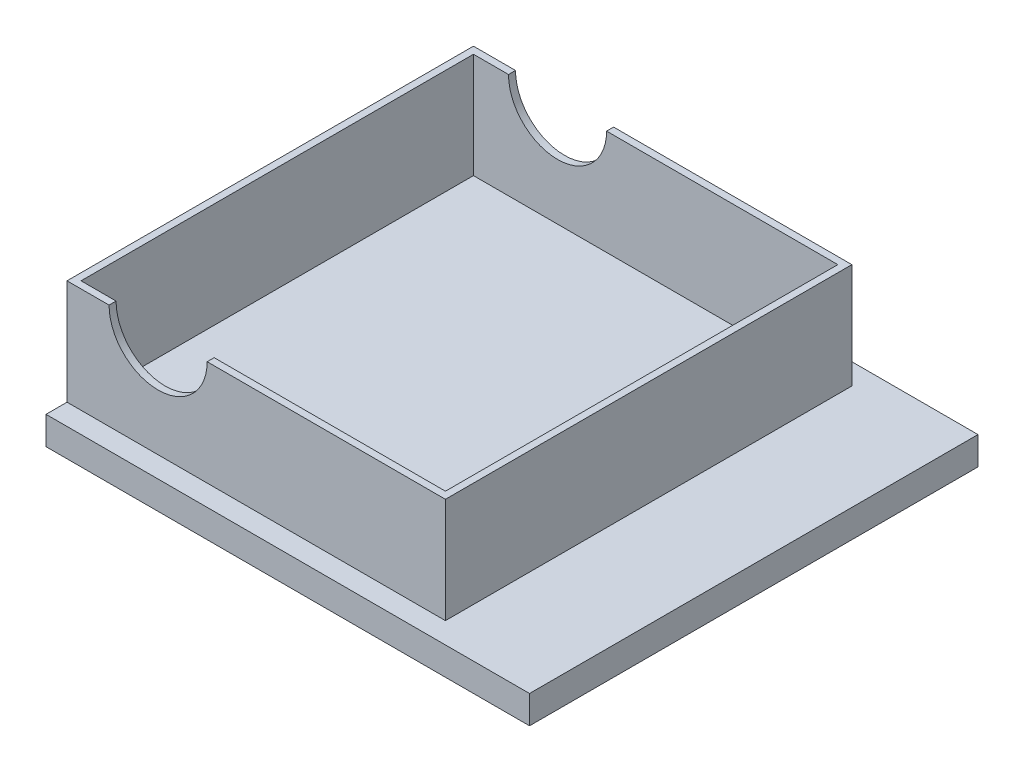
SolidWorks part; units mm, degrees
ref_plane "Plan de face" through (0, 0, 0) normal (0, 0, 1) x (1, 0, 0)
ref_plane "Plan de dessus" through (0, 0, 0) normal (0, 1, 0) x (1, 0, 0)
ref_plane "Plan de droite" through (0, 0, 0) normal (1, 0, 0) x (0, 0, -1)
sketch "Esquisse1" plane through (0, 0, 0) normal (0, 1, 0) x (1, 0, 0)
  line L0 (-20.4211, 25.2895) -> (6.0789, 25.2895)
  line L1 (6.0789, 25.2895) -> (6.0789, -2.7105)
  line L2 (6.0789, -2.7105) -> (-20.4211, -2.7105)
  line L3 (-20.4211, -2.7105) -> (-20.4211, 25.2895)
  line L4 (-20.4211, 25.2895) -> (-20.4211, 27.2895)
  line L5 (-20.4211, 27.2895) -> (14.0789, 27.2895)
  line L6 (14.0789, 27.2895) -> (14.0789, -4.7105)
  line L7 (14.0789, -4.7105) -> (-20.4211, -4.7105)
  line L8 (-20.4211, -4.7105) -> (-20.4211, -2.7105)
  line L9 (-20.4211, -2.7105) -> (-20.4211, -3.2105)
  line L10 (-20.4211, -3.2105) -> (6.5789, -3.2105)
  line L11 (6.5789, -3.2105) -> (6.5789, 25.7895)
  line L12 (6.5789, 25.7895) -> (-20.4211, 25.7895)
  line L13 (-19.9211, -2.7105) -> (-19.9211, 25.2895)
  line L14 (-15.9211, 25.2895) -> (-15.9211, 25.7895)
  line L15 (-8.9211, 25.2895) -> (-8.9211, 25.7895)
  line L16 (-8.9211, -3.2105) -> (-8.9211, -2.7105)
  line L17 (-15.9211, -2.7105) -> (-15.9211, -3.2105)
  point P14 (-15.9211, 25.2895)
  point P15 (-8.9211, 25.2895)
  point P20 (-15.9211, -2.7105)
  point P21 (-8.9211, -2.7105)
  dimension "D1" = 2
  dimension "D2" = 2
  dimension "D3" = 8
  dimension "D4" = 28
  dimension "D5" = 26
  dimension "D6" = 0.5
  dimension "D7" = 0.5
  dimension "D8" = 0.5
  dimension "D9" = 0.5
  dimension "D10" = 7
  dimension "4" = 4
  dimension "D11" = 4
  dimension "D12" = 7
extrude "Boss.-Extru.1" add sketch "Esquisse1" along normal blind 2 contours L3 L2 L1 L0 | L2 L13 L0 L3 | L2 L17 L10 L16 | L16 L10 L11 L12 L15 L0 L1 L2 | L0 L15 L12 L14 | L0 L14 L12 L4 | L17 L2 L8 L10 | L12 L11 L10 L8 L7 L6 L5 L4 region at (-18.1711, 0, -25.5395) region at (-20.1711, 0, -11.2895) region at (-6.9211, 0, -11.2895) region at (-18.1711, 0, 2.9605) region at (-19.9505, 0, -26.5395) region at (-12.4211, 0, -25.5395) region at (-8.5922, 0, -25.5395) region at (-12.4211, 0, 2.9605)
extrude "Boss.-Extru.2" add sketch "Esquisse1<4>" along normal blind 9.5 contours L11 L12 L4 L0 L1 L2 L8 L10 | L2 L13 L0 L3 | L0 L14 L12 L4 | L17 L2 L8 L10 | L2 L17 L10 L16 | L0 L15 L12 L14 region at (-18.1711, 0, -25.5395) region at (-20.1711, 0, -11.2895) region at (-18.1711, 0, 2.9605) region at (-12.4211, 0, -25.5395) region at (-8.5922, 0, -25.5395) region at (-12.4211, 0, 2.9605)
sketch "Esquisse1<4>" plane through (0, 0, 0) normal (0, 1, 0) x (1, 0, 0) same geometry as "Esquisse1"
sketch "Esquisse5" plane through (0, 0, -25.7895) normal (0, 0, -1) x (-1, 0, 0)
  line L0 (20.4211, 2) -> (-6.5789, 2) construction
  line L1 (20.4211, 2) -> (-14.0789, 2) construction
  line L2 (13.9211, 2) -> (13.9211, 9.5)
  circle A0 centre (13.9211, 9.5) radius 3.5
  point P0 (16.4211, 2)
  point P1 (13.9211, 2)
  dimension "D4" = 7
  dimension "D1" = 4
  dimension "D2" = 2.5
  dimension "D3" = 7.5
sketch "Esquisse6" plane through (0, 0, 3.2105) normal (0, 0, 1) x (1, 0, 0)
  circle A0 centre (-13.9211, 9.5) radius 3.5
  point P0 (-20.4211, 2)
  point P1 (-16.4211, 2)
  point P3 (-13.9211, 2)
  point P5 (-13.9211, 9.5)
  dimension "D1" = 7
extrude "Enlèv. mat.-Extru.2" cut sketch "Esquisse6" against normal blind 0.5
extrude "Enlèv. mat.-Extru.3" cut sketch "Esquisse5" against normal blind 0.5 contours A0
